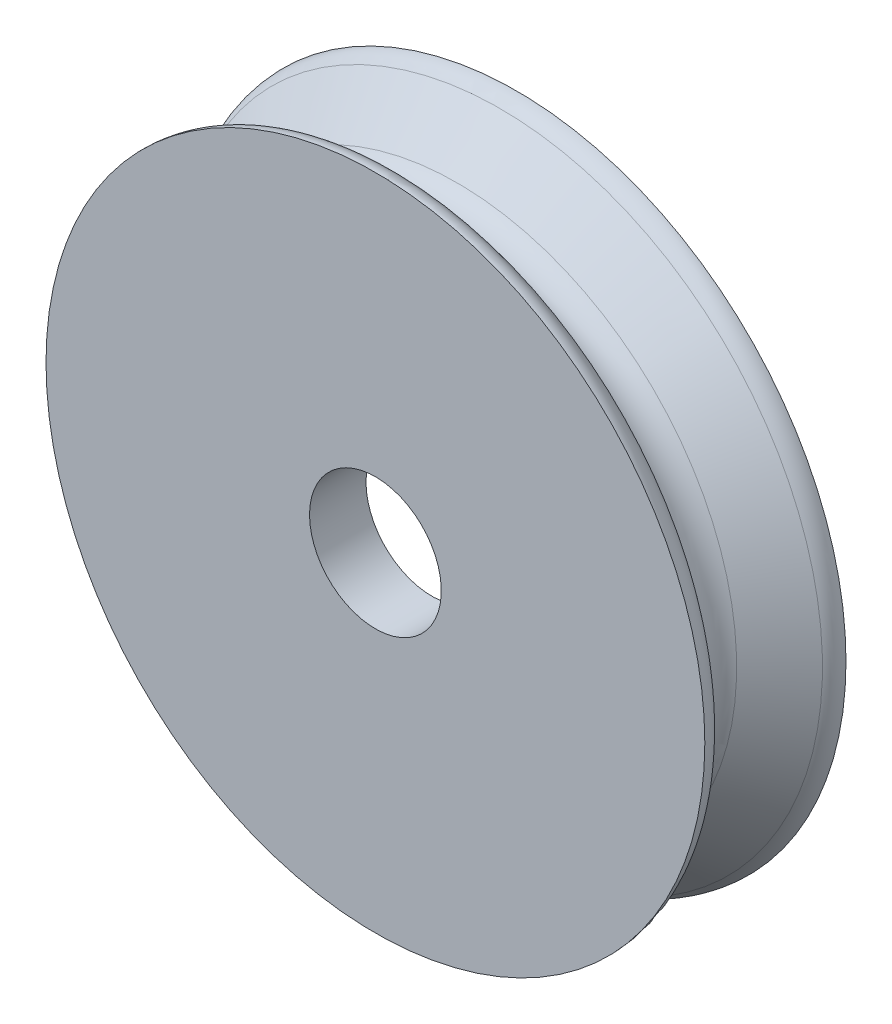
SolidWorks part; units mm, degrees
ref_plane "Front Plane" through (0, 0, 0) normal (0, 0, 1) x (1, 0, 0)
ref_plane "Top Plane" through (0, 0, 0) normal (0, 1, 0) x (1, 0, 0)
ref_plane "Right Plane" through (0, 0, 0) normal (1, 0, 0) x (0, 0, -1)
sketch "Sketch1" plane through (0, 0, 0) normal (1, 0, 0) x (0, 0, -1)
  line L0 (-3.6, 2.8) -> (-6, 2.8)
  line L1 (-6, 2.8) -> (-6, 14)
  line L2 (-5.0341, 13.2588) -> (-4.8308, 12.5002)
  line L3 (-2.5304, 11.8838) -> (-0.7071, 13.7071)
  line L4 (0, 14) -> (0, 12.1515)
  line L5 (0, 0) -> (-11.3925, 0) construction
  line L6 (0, 12.1515) -> (-3.6, 8.5515)
  line L7 (-3.6, 8.5515) -> (-3.6, 2.8)
  arc A0 (-6, 14) -> (-5.0341, 13.2588) centre (-6, 13) cw
  arc A1 (-4.8308, 12.5002) -> (-2.5304, 11.8838) centre (-3.5027, 12.8561) ccw
  arc A2 (-0.7071, 13.7071) -> (0, 14) centre (0, 13) cw
  point P15 (-2.4588, 2.6)
  dimension "D1" = 2.8
  dimension "D5" = 1.375
  dimension "D6" = 14
  dimension "D7" = 1
  dimension "D2" = 6
  dimension "D3" = 15
  dimension "D4" = 45
  dimension "D8" = 1.6
  dimension "D9" = 3.6
revolve "Revolve1" add sketch "Sketch1" angle 360 about L5
